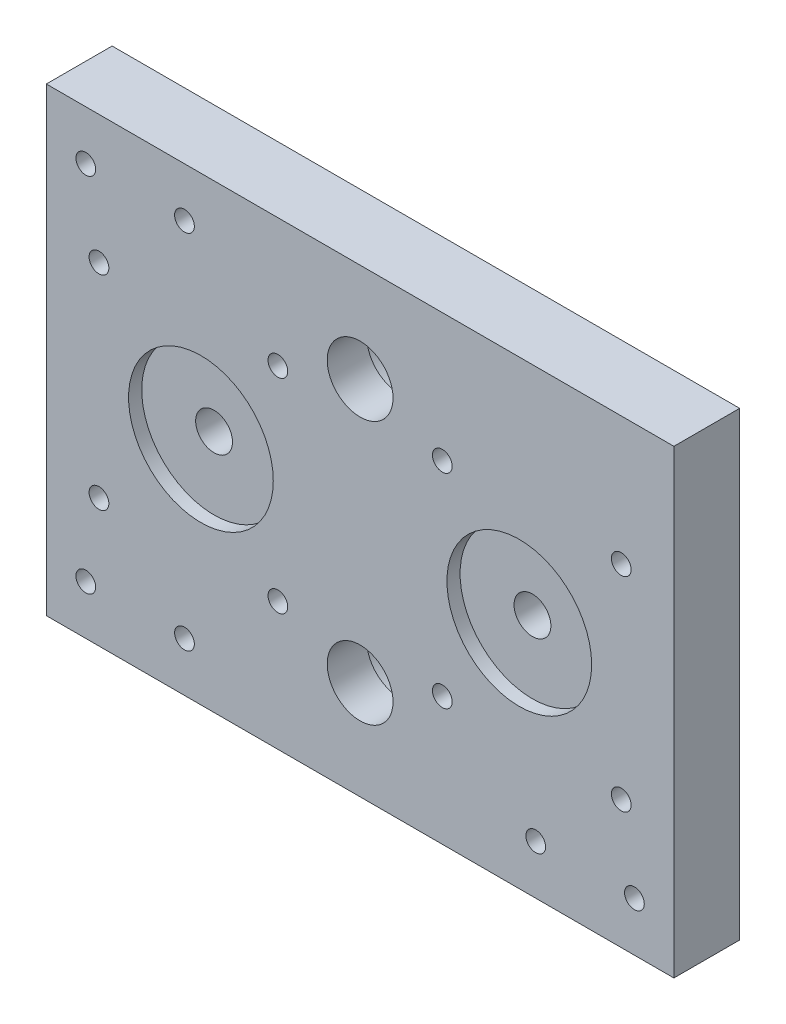
SolidWorks part; units mm, degrees
ref_plane "Front Plane" through (0, 0, 0) normal (0, 0, 1) x (1, 0, 0)
ref_plane "Top Plane" through (0, 0, 0) normal (0, 1, 0) x (1, 0, 0)
ref_plane "Right Plane" through (0, 0, 0) normal (1, 0, 0) x (0, 0, -1)
sketch "Sketch1" plane through (0, 0, 0) normal (0, 0, 1) x (1, 0, 0)
  line L0 (0, 0) -> (0, 40) construction
  line L2 (12.5, -15) -> (-12.5, -15)
  line L3 (12.5, -15) -> (12.5, 55)
  line L4 (12.5, 55) -> (-12.5, 55)
  line L5 (-12.5, -15) -> (-12.5, 55)
  line L6 (12.5, -15) -> (-12.5, 55) construction
  line L7 (12.5, 55) -> (-12.5, -15) construction
  circle A0 centre (0, 40) radius 7.9375
  circle A1 centre (0, 0) radius 7.9375
  point P5 (0, 20)
  dimension "D2" = 15.875
  dimension "D1" = 40
  dimension "D3" = 70
  dimension "D4" = 25
extrude "Boss-Extrude1" add sketch "Sketch1" along normal blind 10
sketch "Sketch2" plane through (0, 0, 10) normal (0, 0, 1) x (1, 0, 0)
  line L0 (12.5, 55) -> (-12.5, 55) construction
  line L1 (-47.7, 55) -> (-8.2, 55)
  line L3 (-47.7, -15) -> (-8.2, -15)
  line L4 (-8.2, 55) -> (-8.2, 36.9142)
  line L5 (-39.7, 35.5) -> (-8.7, 4.5) construction
  line L6 (-39.7, 4.5) -> (-8.7, 35.5) construction
  line L7 (-12.5, -15) -> (12.5, -15) construction
  line L8 (-8.2, 34.0858) -> (-8.2, 5.9142)
  line L9 (0, 55) -> (0, -15) construction
  line L10 (-8.7, 4.5) -> (-39.7, 4.5) construction
  line L11 (-8.7, 4.5) -> (-8.7, 35.5) construction
  line L12 (-8.7, 35.5) -> (-39.7, 35.5) construction
  line L13 (-39.7, 4.5) -> (-39.7, 35.5) construction
  line L14 (-8.7, 4.5) -> (-39.7, 35.5) construction
  line L15 (-8.7, 35.5) -> (-39.7, 4.5) construction
  line L16 (8.7, 35.5) -> (39.7, 4.5) construction
  line L17 (8.7, 4.5) -> (39.7, 35.5) construction
  line L18 (39.7, 4.5) -> (39.7, 35.5) construction
  line L19 (8.7, 35.5) -> (39.7, 35.5) construction
  line L20 (8.7, 4.5) -> (8.7, 35.5) construction
  line L21 (8.7, 4.5) -> (39.7, 4.5) construction
  line L22 (39.7, 4.5) -> (8.7, 35.5) construction
  line L23 (39.7, 35.5) -> (8.7, 4.5) construction
  line L24 (8.2, 55) -> (8.2, 36.9142)
  line L25 (47.7, -15) -> (8.2, -15)
  line L27 (47.7, 55) -> (8.2, 55)
  line L28 (-47.7, 55) -> (-47.7, -15)
  line L29 (47.7, 55) -> (47.7, -15)
  line L31 (-8.2, 3.0858) -> (-8.2, -15)
  line L32 (8.2, 3.0858) -> (8.2, -15)
  line L33 (8.2, 34.0858) -> (8.2, 5.9142)
  circle A0 centre (-39.7, 35.5) radius 1.5
  arc A1 (-8.2, 36.9142) -> (-8.2, 34.0858) centre (-8.7, 35.5) ccw
  arc A2 (-8.2, 5.9142) -> (-8.2, 3.0858) centre (-8.7, 4.5) ccw
  circle A3 centre (-39.7, 4.5) radius 1.5
  circle A4 centre (39.7, 4.5) radius 1.5
  arc A5 (8.2, 5.9142) -> (8.2, 3.0858) centre (8.7, 4.5) cw
  arc A6 (8.2, 36.9142) -> (8.2, 34.0858) centre (8.7, 35.5) cw
  circle A7 centre (39.7, 35.5) radius 1.5
  circle A8 centre (-24.2, 20) radius 2.8
  circle A9 centre (24.2, 20) radius 2.8
  point P0 (-24.2, 20)
  point P11 (-24.2, 20)
  point P34 (24.2, 20)
  dimension "D2" = 3
  dimension "D3" = 5.6
  dimension "D1" = 31
  dimension "D4" = 0.5
  dimension "D5" = 8
  dimension "D6" = 8.2
extrude "Boss-Extrude2" add sketch "Sketch2" against normal up to surface (10 mm away) up to face at (0, 20, 0)
sketch "Sketch6" plane through (0, 0, 10) normal (0, 0, 1) x (1, 0, 0)
  circle A0 centre (-12.5, 35.5) radius 1.5
  circle A1 centre (12.5, 35.5) radius 1.5
  circle A2 centre (-12.5, 4.5) radius 1.5
  circle A3 centre (12.5, 4.5) radius 1.5
  circle A5 centre (-39.7, 35.5) radius 1.5 construction
extrude "Cut-Extrude3" cut sketch "Sketch6" against normal up to surface (10 mm away) up to face at (0, 20, 0)
sketch "Sketch3" plane through (0, 0, 10) normal (0, 0, 1) x (1, 0, 0)
  circle A0 centre (0, 40) radius 7.9375
  circle A1 centre (0, 0) radius 7.9375
  circle A2 centre (0, 40) radius 7.9375 construction
  circle A3 centre (0, 40) radius 5
  circle A4 centre (0, 0) radius 5
  circle A8 centre (0, 0) radius 7.9375 construction
  dimension "D1" = 10
extrude "Boss-Extrude3" add sketch "Sketch3" against normal blind 6.0216
sketch "Sketch4" plane through (0, 0, 10) normal (0, 0, 1) x (1, 0, 0)
  circle A0 centre (-24.2, 20) radius 11
  circle A1 centre (24.2, 20) radius 11
  dimension "D1" = 22
extrude "Cut-Extrude1" cut sketch "Sketch4" against normal blind 2
sketch "Sketch5" plane through (0, 0, 0) normal (0, 0, -1) x (-1, 0, 0)
  circle A0 centre (-39.7, 35.5) radius 2.75
  circle A1 centre (-12.5, 35.5) radius 2.75
  circle A2 centre (-39.7, 4.5) radius 2.75
  circle A3 centre (-12.5, 4.5) radius 2.75
  circle A4 centre (12.5, 35.5) radius 2.75
  circle A5 centre (39.7, 35.5) radius 2.75
  circle A6 centre (12.5, 4.5) radius 2.75
  circle A7 centre (39.7, 4.5) radius 2.75
  circle A9 centre (12.5, 4.5) radius 1.5 construction
  circle A10 centre (-12.5, 4.5) radius 1.5 construction
  circle A11 centre (-12.5, 35.5) radius 1.5 construction
  circle A12 centre (12.5, 35.5) radius 1.5 construction
  dimension "D1" = 5.5
extrude "Cut-Extrude2" cut sketch "Sketch5" against normal blind 3.1
sketch "Sketch11" plane through (0, 0, 0) normal (0, 0, -1) x (-1, 0, 0)
  circle A0 centre (-24.2, 20) radius 10.2
  circle A1 centre (24.2, 20) radius 10.2
  dimension "D1" = 20.4
extrude "Cut-Extrude6" cut sketch "Sketch11" against normal blind 2
sketch "Sketch12" plane through (0, 0, 0) normal (0, 0, -1) x (-1, 0, 0)
  circle A0 centre (24.2, 20) radius 12.5
  dimension "D1" = 25
extrude "Cut-Extrude8" cut sketch "Sketch12" against normal up to surface (2 mm away) up to face at (-34.4, 20, 2)
sketch "Sketch13" plane through (0, 0, 10) normal (0, 0, 1) x (1, 0, 0)
  line L0 (-39.7, 4.5) -> (-41.7, -7.5) construction
  line L1 (-41.7, -7.5) -> (-26.7, -7.5) construction
  line L2 (-26.7, -7.5) -> (-25.8262, -6.2808) construction
  line L3 (25.8262, -6.2808) -> (26.7, -7.5) construction
  line L4 (26.7, -7.5) -> (41.7, -7.5) construction
  line L5 (41.7, -7.5) -> (39.7, 4.5) construction
  line L6 (-39.7, 35.5) -> (-41.7, 47.5) construction
  line L7 (-41.7, 47.5) -> (-26.7, 47.5) construction
  line L8 (-26.7, 47.5) -> (-25.8262, 46.2808) construction
  line L9 (-47.7, 55) -> (-47.7, -15) construction
  line L10 (47.7, -15) -> (47.7, 55) construction
  circle A0 centre (-41.7, -7.5) radius 1.5
  circle A1 centre (-26.7, -7.5) radius 1.5
  circle A2 centre (26.7, -7.5) radius 1.5
  circle A3 centre (41.7, -7.5) radius 1.5
  circle A4 centre (-41.7, 47.5) radius 1.5
  circle A5 centre (-26.7, 47.5) radius 1.5
  dimension "D1" = 3
  dimension "D2" = 15
  dimension "D3" = 15
  dimension "D4" = 12
  dimension "D5" = 6
  dimension "D6" = 6
extrude "Cut-Extrude9" cut sketch "Sketch13" against normal up to surface (10 mm away) up to face at (-36.7, 20, 0)
